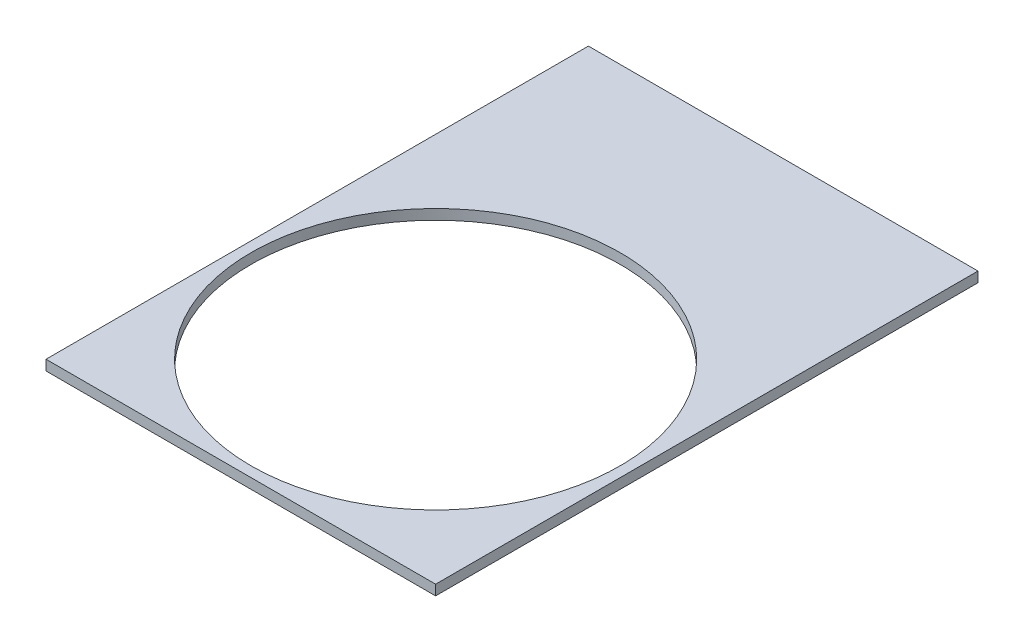
SolidWorks part; units mm, degrees
ref_plane "Front Plane" through (0, 0, 0) normal (0, 0, 1) x (1, 0, 0)
ref_plane "Top Plane" through (0, 0, 0) normal (0, 1, 0) x (1, 0, 0)
ref_plane "Right Plane" through (0, 0, 0) normal (1, 0, 0) x (0, 0, -1)
sketch "Sketch1" plane through (0, 0, 0) normal (0, 1, 0) x (1, 0, 0)
  line L0 (114.497, 374.8331) -> (357.3845, 374.8331)
  line L5 (114.497, 374.8331) -> (114.497, 36.6956)
  line L6 (114.497, 36.6956) -> (357.3845, 36.6956)
  line L7 (357.3845, 374.8331) -> (357.3845, 36.6956)
  circle A0 centre (235.9407, 158.1394) radius 115.0937
extrude "Boss-Extrude1" add sketch "Sketch1" along normal blind 6.35
sketch "Sketch7" plane through (0, 0, 0) normal (0, -1, 0) x (1, 0, 0)
  line L0 (146.247, -36.6956) -> (146.247, -62.0956)
  line L1 (146.247, -62.0956) -> (120.847, -62.0956)
  line L2 (120.847, -36.6956) -> (120.847, -62.0956)
  line L3 (120.847, -62.0956) -> (146.247, -36.6956)
  circle A0 centre (114.497, -36.6956) radius 31.75
  circle A1 centre (146.247, -36.6956) radius 25.4
